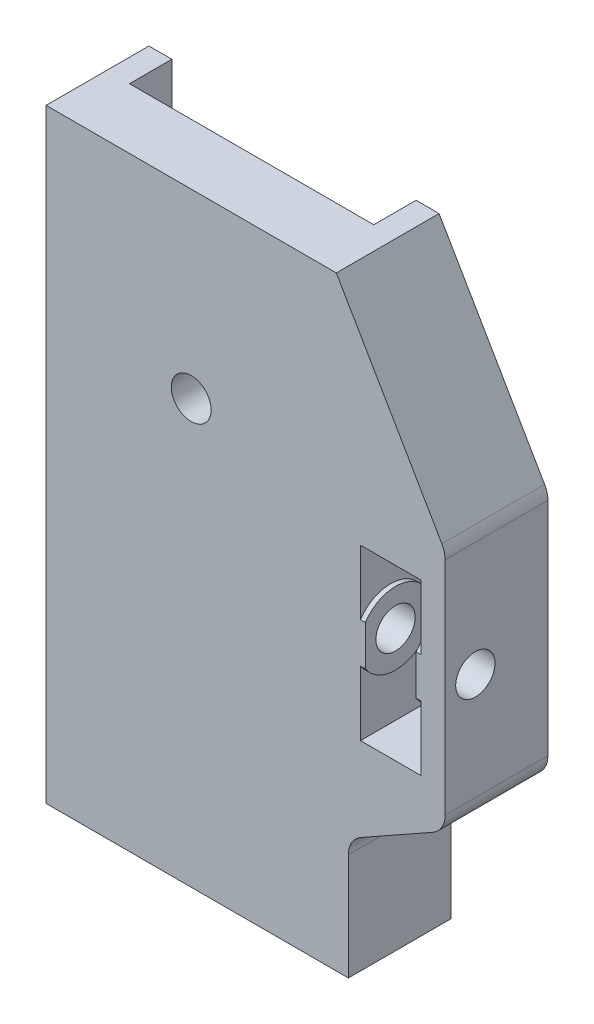
SolidWorks part; units mm, degrees
material "ABS"
ref_plane "前视基准面" through (0, 0, 0) normal (0, 0, 1) x (1, 0, 0)
ref_plane "上视基准面" through (0, 0, 0) normal (0, 1, 0) x (1, 0, 0)
ref_plane "右视基准面" through (0, 0, 0) normal (1, 0, 0) x (0, 0, -1)
other "Configuration Table"
sketch "草图1" plane through (0, 0, 0) normal (0, 0, 1) x (1, 0, 0)
  line L0 (33, 34.5) -> (24, 50)
  line L1 (24, 50) -> (0, 50)
  line L2 (0, 50) -> (0, 0)
  line L5 (33, 14.5) -> (33, 34.5)
  line L6 (26, 17.5) -> (31, 17.5)
  line L7 (26, 31.5) -> (26, 17.5)
  line L12 (31, 31.5) -> (26, 31.5)
  line L17 (31, 17.5) -> (31, 31.5)
  line L18 (0, 0) -> (25, 0)
  line L20 (25, 0) -> (33, 14.5) construction
  line L24 (0, 0) -> (25, 0)
  line L25 (33, 14.5) -> (33, 34.5)
  line L26 (33, 34.5) -> (24, 50)
  line L27 (33, 14.5) -> (25, 10)
  line L28 (25, 10) -> (25, 0)
  circle A0 centre (12, 35) radius 1.65
  dimension "D5" = 3.3
  dimension "D6" = 12
  dimension "D7" = 15
  dimension "D2" = 50
  dimension "D3" = 90
  dimension "D4" = 14.5
  dimension "D8" = 18.5
  dimension "D9" = 26
  dimension "D10" = 5
  dimension "D11" = 14
  dimension "D12" = 25
  dimension "D13" = 33
  dimension "D14" = 4.5
  dimension "D15" = 20
  dimension "D16" = 24
  dimension "D17" = 5
extrude "凸台-拉伸1" add sketch "草图1" against normal blind 8.5 contours L18 L20 L5 L0 L1 L2 A0 L17 L6 L7 L12 region at (14.3684, 25.2914, 0)
sketch "草图2" plane through (0, 50, 0) normal (0, 1, 0) x (1, 0, 0)
  line L0 (24, 8.5) -> (0, 8.5) construction
  line L1 (1.9, 8.5) -> (22.1, 8.5)
  line L2 (1.9, 8.5) -> (1.9, 5)
  line L3 (1.9, 5) -> (22.1, 5)
  line L4 (22.1, 8.5) -> (22.1, 5)
  line L5 (0, 8.5) -> (0, 0) construction
  dimension "D1" = 1.9
  dimension "D2" = 20.2
  dimension "D3" = 3.5
extrude "切除-拉伸1" cut sketch "草图2" against normal through all
sketch "草图3" plane through (33, 0, 0) normal (1, 0, 0) x (0, 0, -1)
  line L0 (0, 14.5) -> (0, 34.5) construction
  circle A0 centre (2.5, 24.5) radius 1.625
  dimension "D1" = 3.25
  dimension "D2" = 2.5
  dimension "D3" = 7
extrude "切除-拉伸2" cut sketch "草图3" against normal up to surface (7 mm away) up to face at (26, 24.5, -4.25)
sketch "草图4" plane through (26, 0, 0) normal (1, 0, 0) x (0, 0, -1)
  circle A0 centre (2.5, 24.5) radius 1
  dimension "D1" = 2
extrude "切除-拉伸3" cut sketch "草图4" against normal up to surface (3.9 mm away) up to face at (22.1, 25, -6.75)
sketch "草图5" plane through (26, 0, 0) normal (1, 0, 0) x (0, 0, -1)
  line L0 (0, 31.5) -> (0, 17.5) construction
  line L1 (0, 26.1583) -> (0, 22.8417)
  arc A0 (0, 22.8417) -> (0, 26.1583) centre (2.5, 24.5) ccw
  circle A2 centre (2.5, 24.5) radius 1 construction
  circle A3 centre (2.5, 24.5) radius 1
  dimension "D1" = 6
extrude "凸台-拉伸2" add sketch "草图5" along normal blind 0.4
sketch "草图6" plane through (31, 0, 0) normal (-1, 0, 0) x (0, 0, 1)
  line L0 (0, 17.5) -> (0, 31.5) construction
  line L1 (0, 22.8417) -> (0, 26.1583)
  circle A0 centre (-2.5, 24.5) radius 1.625 construction
  circle A1 centre (-2.5, 24.5) radius 1.625
  arc A2 (0, 26.1583) -> (0, 22.8417) centre (-2.5, 24.5) ccw
  dimension "D1" = 6
extrude "凸台-拉伸3" add sketch "草图6" along normal blind 0.4
fillet "圆角1" radius 2 3 edges at (33, 34.5, -4.25) (25, 10, -4.25) (33, 14.5, -4.25)
sketch "草图7" plane through (33, 0, 0) normal (1, 0, 0) x (0, 0, -1)
  circle A0 centre (2.5, 24.5) radius 1.625 construction
  circle A1 centre (2.5, 24.5) radius 1.625
extrude "切除-拉伸4" cut sketch "草图7" against normal through all
sketch "草图8" plane through (0, 0, -8.5) normal (0, 0, -1) x (-1, 0, 0)
  line L1 (-26, 17.5) -> (-31, 17.5)
  line L2 (-26, 17.5) -> (-26, 6.5916)
  line L3 (-26, 6.5916) -> (-31, 6.5916)
  line L4 (-31, 17.5) -> (-31, 6.5916)
extrude "切除-拉伸5" cut sketch "草图8" against normal blind 2
fillet "圆角2" radius 0.5 2 edges at (31, 13.375, -7.5) (26, 10.5624, -7.5)
fillet "圆角3" radius 1 4 edges at (31.2476, 13.7983, -6.5) (25.9472, 10.6067, -6.5) (31, 15.865, -6.5) (26, 14.1652, -6.5)
